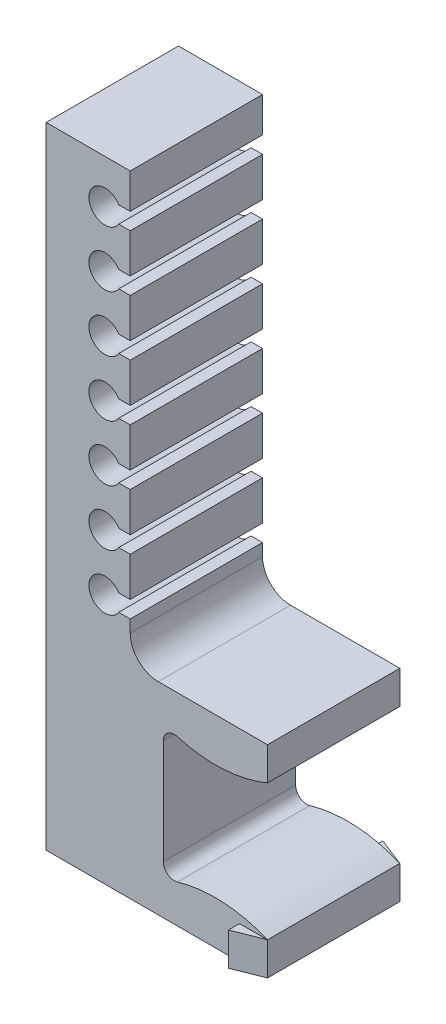
SolidWorks part; units mm, degrees
ref_plane "Front Plane" through (0, 0, 0) normal (0, 0, 1) x (1, 0, 0)
ref_plane "Top Plane" through (0, 0, 0) normal (0, 1, 0) x (1, 0, 0)
ref_plane "Right Plane" through (0, 0, 0) normal (1, 0, 0) x (0, 0, -1)
sketch "Sketch1" plane through (0, 0, 0) normal (0, 0, 1) x (1, 0, 0)
  line L2 (-159.7982, 9.1594) -> (-172.2482, 9.1594)
  line L3 (-172.2482, 9.1594) -> (-172.2482, -9.1594)
  line L7 (-169.2482, -22.8519) -> (-169.2482, 6.1594) construction
  line L13 (-142.8048, 5.1594) -> (-142.8048, -5.1594) construction
  line L23 (-159.7982, 6.1594) -> (-159.7982, 9.1594)
  line L28 (-164.5232, 5.2094) -> (-144.5007, 5.2094) construction
  line L30 (-169.2482, 6.1594) -> (-169.2482, 5.1594)
  line L34 (-169.2482, 5.1594) -> (-169.2482, -5.1594)
  line L35 (-172.2482, 0) -> (-169.2482, 0) construction
  line L36 (-169.2482, -6.1594) -> (-169.2482, -5.1594)
  line L37 (-159.7982, -6.1594) -> (-159.7982, -9.1594)
  line L38 (-159.7982, -9.1594) -> (-172.2482, -9.1594)
  arc A5 (-169.2482, 6.1594) -> (-159.7982, 6.1594) centre (-164.5232, 17.4347) ccw
  arc A6 (-169.2482, -6.1594) -> (-159.7982, -6.1594) centre (-164.5232, -17.4347) cw
  point P30 (-142.8048, 0)
  dimension "D6" = 12.2253
  dimension "D4" = 3
  dimension "D3" = 3
  dimension "D2" = 1
  dimension "D1" = 18.3188
  dimension "D5" = 12.45
extrude "MainBody" add sketch "Sketch1" along normal mid plane 12
sketch "Sketch3" plane through (0, -9.1594, 0) normal (0, -1, 0) x (1, 0, 0)
  line L0 (-159.7982, -6) -> (-162.3382, -7)
  line L1 (-162.3382, -7) -> (-162.3382, -6)
  line L2 (-172.2482, -6) -> (-159.7982, -6) construction
  line L3 (-162.3382, -6) -> (-159.7982, -6)
  line L5 (6.8475, 0) -> (-6.8475, 0) construction
  line L6 (-162.3382, 6) -> (-159.7982, 6)
  line L7 (-162.3382, 7) -> (-162.3382, 6)
  line L8 (-159.7982, 6) -> (-162.3382, 7)
  dimension "D1" = 2.54
  dimension "D2" = 1
extrude "Hook" add sketch "Sketch3" against normal up to vertex (3 mm away) up to point (-159.7982, -6.1594, -6)
fillet "Fillet2" radius 1 2 edges at (-169.2482, 6.1594, 0) (-169.2482, -6.1594, 0)
sketch "Sketch5" [suppressed] plane through (-172.2482, 0, 0) normal (-1, 0, 0) x (0, 0, 1)
  line L1 (-6, 9.1594) -> (6, 9.1594)
  line L2 (-6, 9.1594) -> (-6, -9.1594)
  line L3 (-6, -9.1594) -> (6, -9.1594)
  line L4 (6, 9.1594) -> (6, -9.1594)
extrude "Boss-Extrude1" [suppressed] add sketch "Sketch5" along normal blind 15
sketch "Sketch6" [suppressed] plane through (0, 9.1594, 0) normal (0, 1, 0) x (1, 0, 0)
  line L0 (-187.2482, -6) -> (-187.2482, 6) construction
  circle A0 centre (-182.2482, 0) radius 3.302
  dimension "D1" = 6.604
  dimension "D2" = 5
extrude "Cut-Extrude2" [suppressed] cut sketch "Sketch6" against normal through all
sketch "Sketch7" [suppressed] plane through (-172.2482, 0, 0) normal (-1, 0, 0) x (0, 0, 1)
  circle A0 centre (0, 0) radius 38.1
  dimension "D1" = 76.2
extrude "Boss-Extrude2" [suppressed] add sketch "Sketch7" along normal blind 5
fillet "Fillet3" [suppressed] radius 1
sketch "Sketch8" [suppressed] plane through (0, 0, 6) normal (0, 0, 1) x (1, 0, 0)
  line L6 (-172.2482, -0.635) -> (-173.4343, -0.635)
  line L8 (-172.2482, 0.635) -> (-173.4343, 0.635)
  line L10 (-172.2482, 0.635) -> (-173.4343, 0.635)
  line L11 (-172.2482, 0.635) -> (-172.2482, -0.635)
  line L12 (-162.3382, -9.1594) -> (-162.3382, -6.1594)
  line L14 (-169.2482, -4.7448) -> (-169.2482, 4.7448)
  line L15 (-159.7982, 6.1594) -> (-159.7982, 9.1594)
  line L16 (-159.7982, 9.1594) -> (-172.2482, 9.1594)
  line L17 (-172.2482, 9.1594) -> (-172.2482, -9.1594)
  line L18 (-172.2482, -9.1594) -> (-162.3382, -9.1594)
  line L21 (-169.2482, -4.7448) -> (-169.2482, 4.7448)
  line L22 (-159.7982, 6.1594) -> (-159.7982, 9.1594)
  line L23 (-159.7982, 9.1594) -> (-172.2482, 9.1594)
  line L24 (-172.2482, 9.1594) -> (-172.2482, -9.1594)
  line L25 (-172.2482, -9.1594) -> (-162.3382, -9.1594)
  line L26 (-172.2482, -0.635) -> (-173.4343, -0.635)
  line L32 (-162.3382, -9.1594) -> (-162.3382, -6.1594)
  line L33 (-162.3382, -6.1594) -> (-159.7982, -6.1594)
  line L34 (-162.3382, -6.1594) -> (-159.7982, -6.1594)
  arc A0 (-173.4343, 0.635) -> (-173.4343, -0.635) centre (-174.5342, 0) ccw
  arc A4 (-159.7982, -6.1594) -> (-167.9665, -5.7043) centre (-164.5232, -17.4347) ccw
  arc A6 (-169.2482, -4.7448) -> (-167.9665, -5.7043) centre (-168.2482, -4.7448) ccw
  arc A7 (-167.9665, 5.7043) -> (-159.7982, 6.1594) centre (-164.5232, 17.4347) ccw
  arc A8 (-159.7982, -6.1594) -> (-167.9665, -5.7043) centre (-164.5232, -17.4347) ccw
  arc A11 (-167.9665, 5.7043) -> (-159.7982, 6.1594) centre (-164.5232, 17.4347) ccw
  arc A12 (-169.2482, -4.7448) -> (-167.9665, -5.7043) centre (-168.2482, -4.7448) ccw
  arc A13 (-167.9665, 5.7043) -> (-169.2482, 4.7448) centre (-168.2482, 4.7448) ccw
  arc A14 (-167.9665, 5.7043) -> (-169.2482, 4.7448) centre (-168.2482, 4.7448) ccw
  point P6 (-172.2482, 0)
  line M14 (-172.2482, 9.1594) -> (-172.2482, -9.1594)
  dimension "D2" = 1.27
  dimension "D1" = 0
  dimension "D3" = 2.286
extrude "Slot" [suppressed] add sketch "Sketch8" against normal up to surface (12 mm away) contours L8 A0 L6 M14 up to face at (-165.7635, -0.5599, -6)
sketch "Sketch10" [suppressed] plane through (0, 0, -6) normal (0, 0, -1) x (-1, 0, 0)
  line L0 (166.0232, -9.1594) -> (172.2482, -9.1594)
  line L3 (172.2482, -9.1594) -> (166.0232, -9.1594)
  line L5 (172.2482, -9.1594) -> (187.9767, -44.4861)
  line L6 (195.4932, -61.3685) -> (192.3182, -61.3685)
  line L7 (159.7982, -6.1594) -> (159.7982, -9.1594)
  line L8 (159.7982, -6.1594) -> (159.7982, -9.1594)
  line L9 (159.7982, -9.1594) -> (172.2482, -9.1594)
  line L10 (172.2482, -9.1594) -> (172.2482, 9.1594)
  line L11 (172.2482, 9.1594) -> (159.7982, 9.1594)
  line L12 (159.7982, 9.1594) -> (159.7982, 6.1594)
  line L13 (169.2482, 6.1594) -> (169.2482, -6.1594)
  line L16 (159.7982, -9.1594) -> (172.2482, -9.1594)
  line L17 (172.2482, -9.1594) -> (172.2482, 9.1594)
  line L18 (172.2482, 9.1594) -> (159.7982, 9.1594)
  line L19 (159.7982, 9.1594) -> (159.7982, 6.1594)
  line L20 (169.2482, 6.1594) -> (169.2482, -6.1594)
  line L21 (195.4932, -61.3685) -> (201.8432, -61.3685)
  line L22 (201.8432, -61.3685) -> (201.8432, -59.781)
  line L24 (192.666, -55.0185) -> (200.9772, -55.0185)
  line L25 (169.0732, -9.1594) -> (192.3182, -61.3685)
  line L28 (201.8432, -59.781) -> (194.7864, -59.781)
  line L31 (193.3728, -56.606) -> (200.9772, -56.606)
  line L42 (200.9772, -55.0185) -> (200.9772, -56.606)
  line L43 (187.9767, -44.4861) -> (195.4932, -61.3685)
  arc A4 (169.2482, -6.1594) -> (159.7982, -6.1594) centre (164.5232, -17.4347) ccw
  arc A5 (159.7982, 6.1594) -> (169.2482, 6.1594) centre (164.5232, 17.4347) ccw
  arc A8 (169.2482, -6.1594) -> (159.7982, -6.1594) centre (164.5232, -17.4347) ccw
  arc A9 (159.7982, 6.1594) -> (169.2482, 6.1594) centre (164.5232, 17.4347) ccw
  dimension "D5" = 6.35
  dimension "D7" = 3.175
  dimension "D8" = 3.175
  dimension "D2" = 57.15
  dimension "D10" = 1.5875
  dimension "D13" = 114
  dimension "D14" = 114
  dimension "D3" = 1.5875
  dimension "D4" = 3.175
extrude "Boss-Extrude3" [suppressed] add sketch "Sketch10" against normal up to surface (12 mm away) up to face at (-165.7635, -0.5599, 6)
sketch "Sketch11" [suppressed] plane through (0, 0, -6) normal (0, 0, -1) x (-1, 0, 0)
  line L0 (159.7982, -9.1594) -> (159.7982, 9.1594)
  line L11 (169.2482, 6.1594) -> (169.2482, -6.1594)
  line L12 (159.7982, -6.1594) -> (159.7982, -9.1594)
  line L13 (159.7982, -9.1594) -> (169.0732, -9.1594)
  line L14 (169.0732, -9.1594) -> (192.3182, -61.3685)
  line L15 (192.3182, -61.3685) -> (201.8432, -61.3685)
  line L16 (201.8432, -61.3685) -> (201.8432, -59.781)
  line L17 (201.8432, -59.781) -> (194.7864, -59.781)
  line L18 (194.7864, -59.781) -> (193.3728, -56.606)
  line L19 (172.2482, -9.1594) -> (172.2482, 9.1594)
  line L20 (172.2482, 9.1594) -> (159.7982, 9.1594)
  line L21 (159.7982, 9.1594) -> (159.7982, 6.1594)
  line L22 (169.2482, 6.1594) -> (169.2482, -6.1594)
  line L23 (159.7982, -6.1594) -> (159.7982, -9.1594)
  line L24 (159.7982, -9.1594) -> (169.0732, -9.1594)
  line L25 (169.0732, -9.1594) -> (192.3182, -61.3685)
  line L26 (192.3182, -61.3685) -> (201.8432, -61.3685)
  line L27 (201.8432, -61.3685) -> (201.8432, -59.781)
  line L28 (201.8432, -59.781) -> (194.7864, -59.781)
  line L29 (194.7864, -59.781) -> (193.3728, -56.606)
  line L30 (172.2482, -9.1594) -> (172.2482, 9.1594)
  line L31 (172.2482, 9.1594) -> (159.7982, 9.1594)
  line L32 (159.7982, 9.1594) -> (159.7982, 6.1594)
  line L37 (193.3728, -56.606) -> (200.9772, -56.606)
  line L38 (193.3728, -56.606) -> (200.9772, -56.606)
  line L39 (200.9772, -56.606) -> (200.9772, -55.0185)
  line L40 (200.9772, -56.606) -> (200.9772, -55.0185)
  line L41 (192.666, -55.0185) -> (172.2482, -9.1594)
  line L42 (192.666, -55.0185) -> (172.2482, -9.1594)
  line L44 (200.9772, -55.0185) -> (192.666, -55.0185)
  line L45 (200.9772, -55.0185) -> (192.666, -55.0185)
  arc A2 (159.7982, 6.1594) -> (169.2482, 6.1594) centre (164.5232, 17.4347) ccw
  arc A3 (169.2482, -6.1594) -> (159.7982, -6.1594) centre (164.5232, -17.4347) ccw
  arc A4 (159.7982, 6.1594) -> (169.2482, 6.1594) centre (164.5232, 17.4347) ccw
  arc A5 (169.2482, -6.1594) -> (159.7982, -6.1594) centre (164.5232, -17.4347) ccw
  arc M14 (159.7982, 6.1594) -> (169.2482, 6.1594) centre (164.5232, 17.4347) ccw
  line M15 (169.2482, 6.1594) -> (169.2482, -6.1594)
  arc M16 (169.2482, -6.1594) -> (159.7982, -6.1594) centre (164.5232, -17.4347) ccw
  dimension "D1" = 0
extrude "Boss-Extrude4" [suppressed] add sketch "Sketch11" against normal up to surface (12 mm away) contours L0 M16 M15 M14 up to face at (-165.7635, -0.5599, 6)
sketch "Sketch12" [suppressed] plane through (0, 0, -6) normal (0, 0, -1) x (-1, 0, 0)
  line L0 (159.7982, -9.1594) -> (159.7982, -5.9844)
  line L1 (159.7982, -5.9844) -> (162.0842, -5.9844)
  line L3 (162.0842, -5.2351) -> (159.7982, -5.2351)
  line L4 (162.0842, -5.2351) -> (162.0842, -6.7337)
  line L5 (162.0842, -6.7337) -> (159.7982, -6.7337)
  line L6 (159.7982, -5.2351) -> (159.7982, -6.7337)
  line L7 (162.0842, -5.2351) -> (159.7982, -6.7337) construction
  line L8 (162.0842, -6.7337) -> (159.7982, -5.2351) construction
  line L9 (172.2482, 9.1594) -> (159.7982, 9.1594)
  line L10 (159.7982, 9.1594) -> (159.7982, -9.1594)
  line L11 (159.7982, -9.1594) -> (169.0732, -9.1594)
  line L12 (169.0732, -9.1594) -> (192.3182, -61.3685)
  line L13 (192.3182, -61.3685) -> (201.8432, -61.3685)
  line L14 (201.8432, -61.3685) -> (201.8432, -59.781)
  line L15 (201.8432, -59.781) -> (194.7864, -59.781)
  line L16 (194.7864, -59.781) -> (193.3728, -56.606)
  line L17 (172.2482, -9.1594) -> (172.2482, 9.1594)
  line L18 (172.2482, 9.1594) -> (159.7982, 9.1594)
  line L19 (159.7982, 9.1594) -> (159.7982, -9.1594)
  line L20 (159.7982, -9.1594) -> (169.0732, -9.1594)
  line L21 (169.0732, -9.1594) -> (192.3182, -61.3685)
  line L22 (192.3182, -61.3685) -> (201.8432, -61.3685)
  line L23 (201.8432, -61.3685) -> (201.8432, -59.781)
  line L24 (201.8432, -59.781) -> (194.7864, -59.781)
  line L25 (194.7864, -59.781) -> (193.3728, -56.606)
  line L26 (172.2482, -9.1594) -> (172.2482, 9.1594)
  line L38 (193.3728, -56.606) -> (200.9772, -56.606)
  line L39 (193.3728, -56.606) -> (200.9772, -56.606)
  line L40 (200.9772, -56.606) -> (200.9772, -55.0185)
  line L42 (192.666, -55.0185) -> (172.2482, -9.1594)
  line L43 (192.666, -55.0185) -> (172.2482, -9.1594)
  line L45 (200.9772, -56.606) -> (200.9772, -55.0185)
  line L46 (200.9772, -55.0185) -> (192.666, -55.0185)
  line L47 (200.9772, -55.0185) -> (192.666, -55.0185)
  circle A0 centre (162.0842, -5.9844) radius 1.3843
  point P8 (160.9412, -5.9844)
  line M13 (159.7982, 9.1594) -> (159.7982, -9.1594)
  dimension "D4" = 2.7686
  dimension "D2" = 3.175
  dimension "D3" = 2.286
  dimension "D5" = 1.4986
extrude "Cut-Extrude3" [suppressed] cut sketch "Sketch12" against normal up to surface (12 mm away) contours L5 A0 L3 L4 | L1 A0 L5 L4 | A0 L1 L5 M13 | L3 A0 L1 L4 | A0 L3 L1 M13 up to face at (-165.7635, -0.5599, 6)
pattern_linear "LPattern1" [suppressed] count 4 spacing 4.28 of bodies 117
sketch "Sketch15" plane through (0, 0, 6) normal (0, 0, 1) x (1, 0, 0)
  line L1 (-172.2482, -9.1594) -> (-179.8682, -9.1594)
  line L2 (-172.2482, -9.1594) -> (-172.2482, 47.9906)
  line L3 (-172.2482, 47.9906) -> (-179.8682, 47.9906)
  line L4 (-179.8682, -9.1594) -> (-179.8682, 47.9906)
  dimension "D1" = 7.62
  dimension "D2" = 57.15
extrude "Boss-Extrude6" add sketch "Sketch15" against normal up to surface (12 mm away) up to face at (-165.7635, -0.5599, -6)
sketch "Sketch16" plane through (0, 0, 6) normal (0, 0, 1) x (1, 0, 0)
  line L0 (-172.2482, 9.1594) -> (-172.2482, 47.9906) construction
  line L1 (-172.2482, 44.8156) -> (-174.5342, 44.8156)
  line L2 (-172.2482, 44.8156) -> (-172.2482, 43.2916)
  line L3 (-172.2482, 43.2916) -> (-174.5342, 43.2916)
  line L4 (-174.5342, 44.8156) -> (-174.5342, 43.2916)
  line L5 (-172.2482, 47.9906) -> (-179.8682, 47.9906) construction
  circle A0 centre (-174.5342, 44.0536) radius 1.4605
  line M12 (-172.2482, 9.1594) -> (-172.2482, 47.9906)
  dimension "D4" = 2.921
  dimension "D1" = 3.175
  dimension "D2" = 1.524
  dimension "D3" = 2.286
extrude "Cut-Extrude6" cut sketch "Sketch16" against normal up to surface (12 mm away) contours A0 L3 L1 M12 | L3 A0 L1 L4 | L1 A0 L3 L4 region at (-172.6978, 44.0536, 6) region at (-173.8371, 44.0536, 6) region at (-174.8568, 44.0536, 6) up to face at (-167.9334, 6.9094, -6)
pattern_linear "LPattern3" count 7 spacing 5.08 along (0, -1, 0) of "Cut-Extrude6"
fillet "Fillet5" radius 2.54 1 edges at (-172.2482, 9.1594, 0)
equation "\"HookThickness\"= 3mm"
equation "\"D3@Sketch1\"=\"HookThickness\""
equation "\"D4@Sketch1\"=\"HookThickness\""
equation "\"CylinderDiameter\"=3"
equation "\"D1@Sketch7\"=\"CylinderDiameter\""
equation "\"Mount Tolerance\"= .005in"
equation "\"Mount Thickness\"= .0625in"
equation "\"Mount Angle\"= 114"
equation "\"D14@Sketch10\"=\"Mount Angle\""
equation "\"D13@Sketch10\"= \"Mount Angle\""
equation "\"Joint Radius\"= .05in"
equation "\"Joint Thickness\"= .05in"
equation "\"Joint Tolerance\"= .009in"
equation "\"D4@Sketch12\"= (\"Joint Radius\" * 2) + \"Joint Tolerance\""
equation "\"D5@Sketch12\"= \"Joint Thickness\" + \"Joint Tolerance\""
